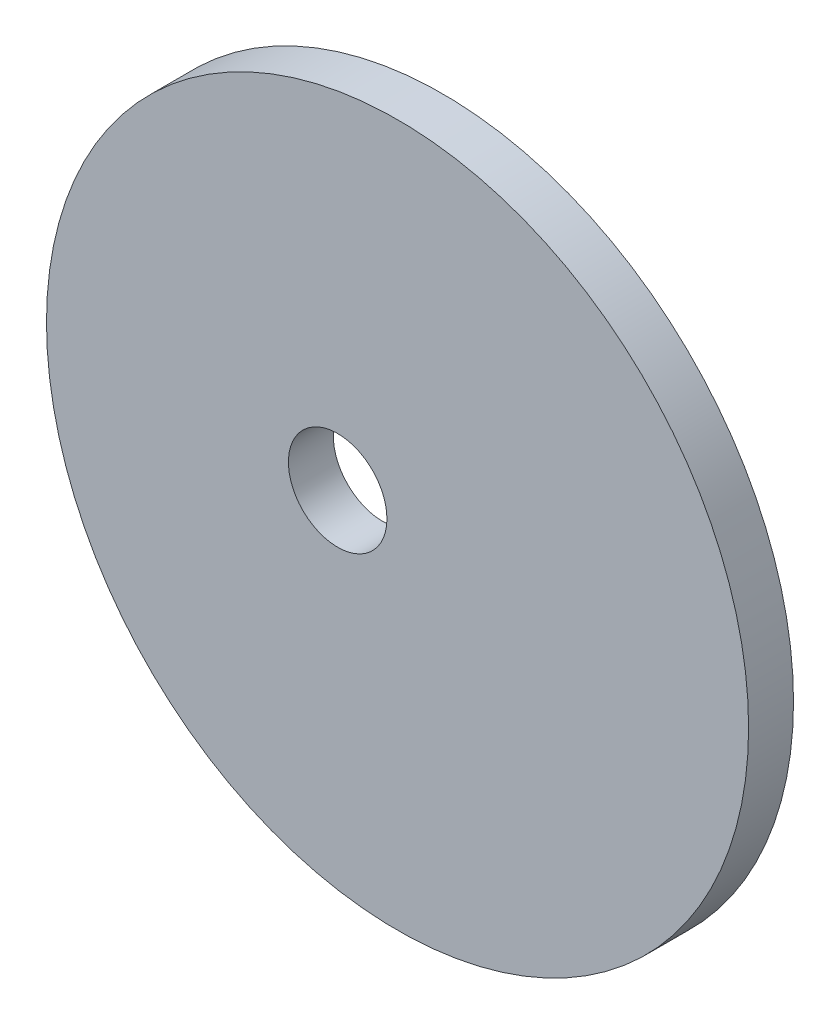
SolidWorks part; units mm, degrees
ref_plane "Front Plane" through (0, 0, 0) normal (0, 0, 1) x (1, 0, 0)
ref_plane "Top Plane" through (0, 0, 0) normal (0, 1, 0) x (1, 0, 0)
ref_plane "Right Plane" through (0, 0, 0) normal (1, 0, 0) x (0, 0, -1)
sketch "Sketch1" plane through (0, 0, 0) normal (0, 0, 1) x (1, 0, 0)
  circle A0 centre (0, 0) radius 23.4531
  circle A2 centre (-4, 0) radius 3.2906
extrude "Boss-Extrude5" add sketch "Sketch1" along normal blind 3 contours A2 | A0 region at (-4, 0, 0)
sketch "Sketch2" plane through (0, 0, 0) normal (0, 0, 1) x (1, 0, 0)
  circle A0 centre (0, 0) radius 23.75
sketch "Sketch3" plane through (0, 0, 0) normal (0, 0, 1) x (1, 0, 0)
  circle A0 centre (-4, 0) radius 3.175
sketch "Sketch4" plane through (0, 0, 0) normal (0, 0, 1) x (1, 0, 0)
  circle A0 centre (0, 0) radius 23.3344
sketch "Sketch5" plane through (0, 0, 0) normal (0, 0, 1) x (1, 0, 0)
  circle A0 centre (0, 0) radius 23.3938
sketch "Sketch6" plane through (0, 0, 0) normal (0, 0, 1) x (1, 0, 0)
  circle A0 centre (0, 0) radius 23.4531
  circle A1 centre (-4, 0) radius 3.2906
extrude "Boss-Extrude9" add sketch "Sketch6" along normal blind 2
